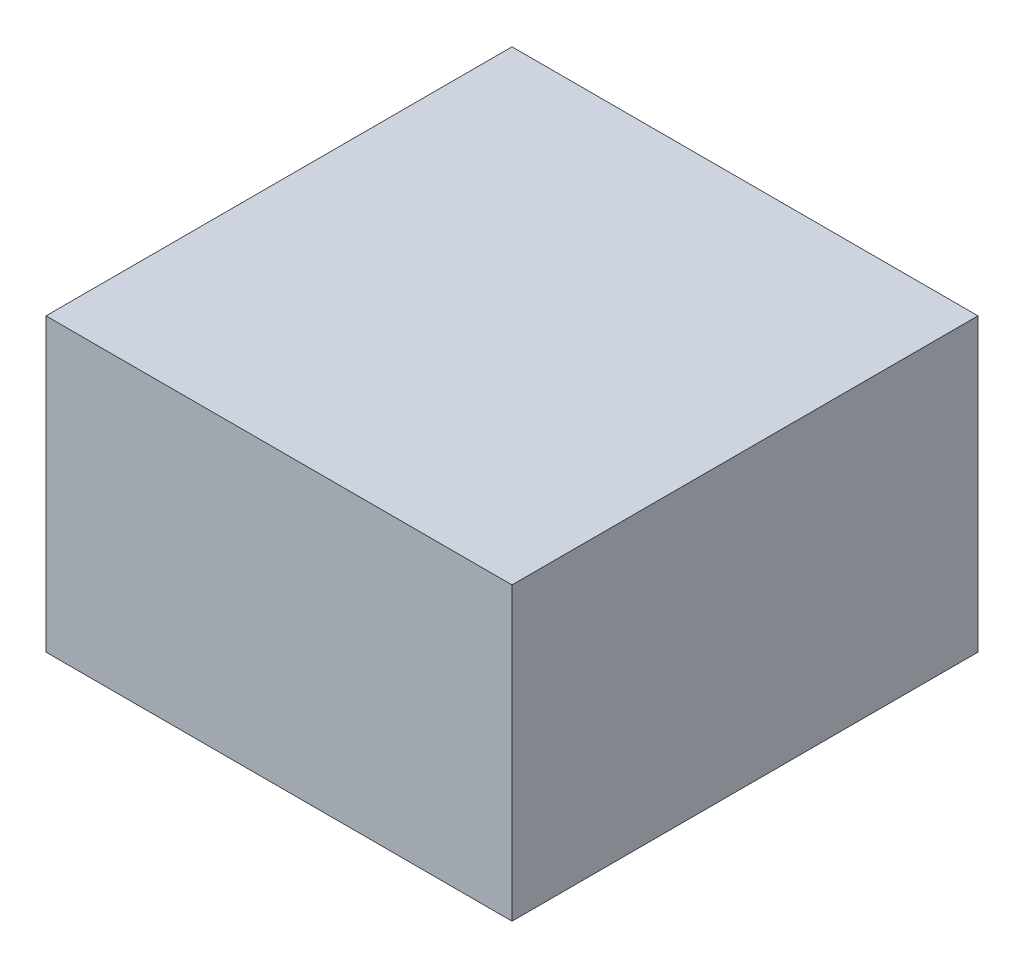
SolidWorks part; units mm, degrees
ref_plane "Front Plane" through (0, 0, 0) normal (0, 0, 1) x (1, 0, 0)
ref_plane "Top Plane" through (0, 0, 0) normal (0, 1, 0) x (1, 0, 0)
ref_plane "Right Plane" through (0, 0, 0) normal (1, 0, 0) x (0, 0, -1)
sketch "Sketch1" plane through (0, 0, 0) normal (0, 1, 0) x (1, 0, 0)
  line L0 (0, -55) -> (0, 55) construction
  line L1 (-101.6, -101.6) -> (101.6, -101.6)
  line L2 (-101.6, -101.6) -> (-101.6, 101.6)
  line L3 (-101.6, 101.6) -> (101.6, 101.6)
  line L4 (101.6, -101.6) -> (101.6, 101.6)
  line L5 (-55, 0) -> (55, 0) construction
  dimension "D1" = 203.2
  dimension "D2" = 203.2
  dimension "D3" = 101.6
  dimension "D4" = 101.6
extrude "Boss-Extrude1" add sketch "Sketch1" along normal blind 63.5 and the other way blind 63.5
